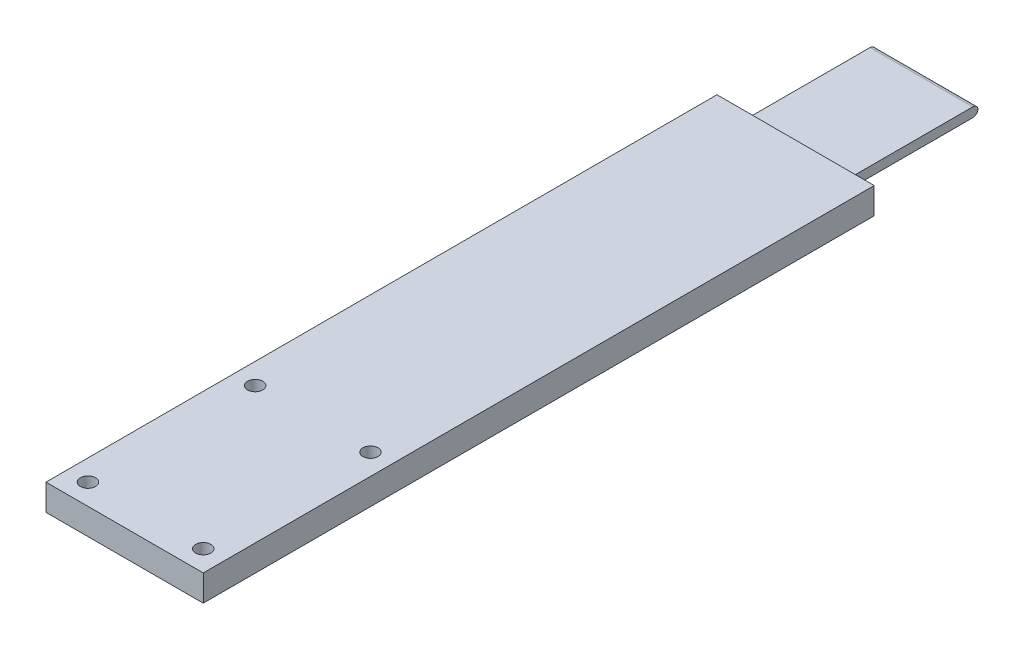
SolidWorks part; units mm, degrees
ref_plane "前视基准面" through (0, 0, 0) normal (0, 0, 1) x (1, 0, 0)
ref_plane "上视基准面" through (0, 0, 0) normal (0, 1, 0) x (1, 0, 0)
ref_plane "右视基准面" through (0, 0, 0) normal (1, 0, 0) x (0, 0, -1)
other "Configuration Table"
sketch "草图1" plane through (0, 0, 0) normal (0, 0, 1) x (1, 0, 0)
  line L1 (0, 0) -> (-30, 0)
  line L2 (0, 0) -> (0, 5)
  line L3 (0, 5) -> (-30, 5)
  line L4 (-30, 0) -> (-30, 5)
  dimension "D1" = 30
  dimension "D2" = 5
extrude "凸台-拉伸1" add sketch "草图1" along normal blind 128
sketch "草图2" plane through (0, 5, 0) normal (0, 1, 0) x (1, 0, 0)
  line L0 (-30, -128) -> (-26, -128) construction
  line L1 (0, -128) -> (-30, -128) construction
  line L2 (-26, -128) -> (-26, -124) construction
  line L3 (-26, -124) -> (-26, -92.1) construction
  line L4 (-15, -128) -> (-15, -30.41) construction
  circle A0 centre (-26, -124) radius 1.45
  circle A1 centre (-26, -92.1) radius 1.45
  circle A2 centre (-4, -124) radius 1.45
  circle A3 centre (-4, -92.1) radius 1.45
  dimension "D4" = 2.9
  dimension "D5" = 2.9
  dimension "D1" = 4
  dimension "D2" = 4
  dimension "D3" = 31.9
extrude "切除-拉伸1" cut sketch "草图2" against normal blind 60
sketch "草图3" plane through (0, 0, 0) normal (0, -1, 0) x (1, 0, 0)
  line L0 (0, 128) -> (0, 0) construction
  line L1 (-30, 0) -> (0, 0)
  line L2 (-30, 0) -> (-30, 10)
  line L3 (-30, 10) -> (0, 10)
  line L4 (0, 0) -> (0, 10)
  dimension "D1" = 10
sketch "草图4" plane through (0, 0, 0) normal (0, 0, -1) x (-1, 0, 0)
  line L0 (30, 5) -> (30, 0) construction
  line L1 (5.2, 3.4) -> (24.8, 3.4)
  line L2 (5.2, 3.4) -> (5.2, 1.6)
  line L3 (5.2, 1.6) -> (24.8, 1.6)
  line L4 (24.8, 3.4) -> (24.8, 1.6)
  line L5 (0, 0) -> (0, 5) construction
  line L6 (0, 5) -> (30, 5) construction
  line L7 (30, 0) -> (0, 0) construction
  dimension "D1" = 5.2
  dimension "D2" = 5.2
  dimension "D3" = 1.6
  dimension "D4" = 1.6
extrude "凸台-拉伸2" add sketch "草图4" along normal blind 25
fillet "圆角1" radius 1 2 edges at (-15, 1.6, -25) (-15, 3.4, -25)
